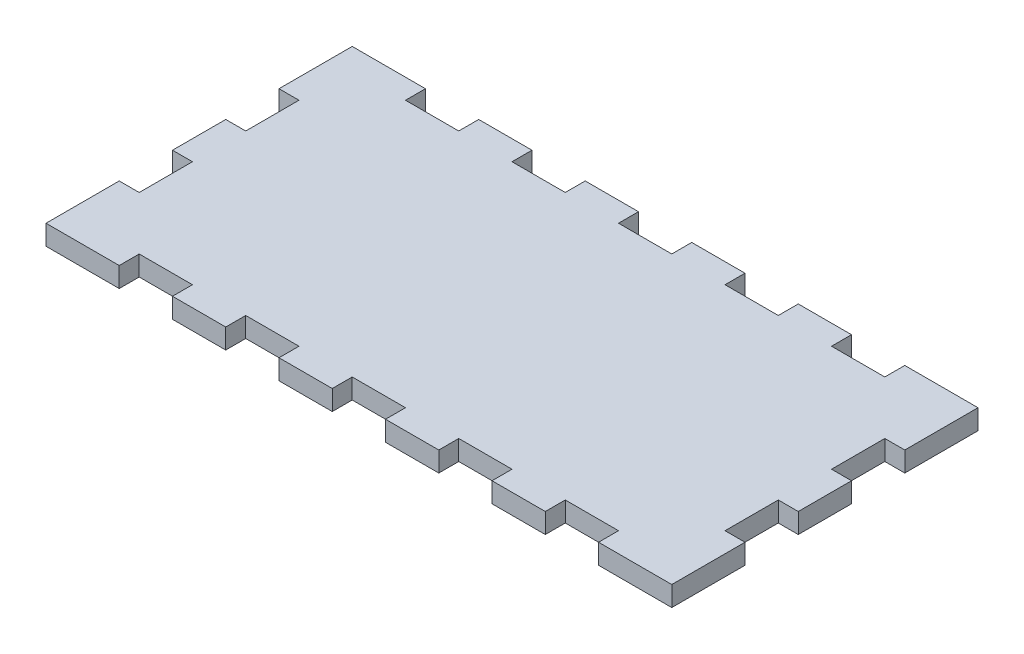
SolidWorks part; units mm, degrees
ref_plane "Front Plane" through (0, 0, 0) normal (0, 0, 1) x (1, 0, 0)
ref_plane "Top Plane" through (0, 0, 0) normal (0, 1, 0) x (1, 0, 0)
ref_plane "Right Plane" through (0, 0, 0) normal (1, 0, 0) x (0, 0, -1)
sketch "Sketch2" plane through (0, 0, 0) normal (0, 1, 0) x (1, 0, 0)
  line L1 (139.7, -63.5) -> (-139.7, -63.5)
  line L2 (139.7, -63.5) -> (139.7, 63.5)
  line L3 (139.7, 63.5) -> (-139.7, 63.5)
  line L4 (-139.7, -63.5) -> (-139.7, 63.5)
  line L5 (139.7, -63.5) -> (-139.7, 63.5) construction
  line L6 (139.7, 63.5) -> (-139.7, -63.5) construction
  point P0 (0, 0)
  dimension "D1" = 279.4
  dimension "D2" = 127
extrude "Boss-Extrude1" add sketch "Sketch2" along normal blind 9.525
sketch "Sketch3" plane through (0, 0, 63.5) normal (0, 0, 1) x (1, 0, 0)
  line L0 (-139.7, 9.525) -> (139.7, 9.525) construction
  line L1 (-139.7, 0) -> (-114.3, 0)
  line L2 (-139.7, 0) -> (-139.7, 9.525)
  line L3 (-139.7, 9.525) -> (-114.3, 9.525)
  line L4 (-114.3, 0) -> (-114.3, 9.525)
  dimension "D1" = 25.4
extrude "Boss-Extrude2" add sketch "Sketch3" along normal blind 9.525
pattern_linear "LPattern1" count 6 spacing 50.8 along (1, 0, 0) of "Boss-Extrude2"
mirror "Mirror1" about plane through (0, 0, 0) normal (0, 0, 1) of "LPattern1"
sketch "Sketch4" plane through (139.7, 0, 0) normal (1, 0, 0) x (0, 0, -1)
  line L0 (-73.025, 0) -> (73.025, 0) construction
  line L1 (-63.5, 0) -> (-38.1, 0)
  line L2 (-63.5, 0) -> (-63.5, 9.525)
  line L3 (-63.5, 9.525) -> (-38.1, 9.525)
  line L4 (-38.1, 0) -> (-38.1, 9.525)
  line L5 (-73.025, 9.525) -> (73.025, 9.525) construction
  line L6 (-73.025, 0) -> (-73.025, 9.525) construction
  dimension "D1" = 9.525
  dimension "D2" = 25.4
extrude "Boss-Extrude3" add sketch "Sketch4" along normal blind 9.525
pattern_linear "LPattern2" count 3 spacing 50.8 along (0, 0, -1) of "Boss-Extrude3"
mirror "Mirror2" about plane through (0, 0, 0) normal (1, 0, 0) of "LPattern2"
sketch "Sketch6" plane through (0, 0, 63.5) normal (0, 0, 1) x (1, 0, 0)
  line L1 (149.225, 9.525) -> (139.7, 9.525)
  line L2 (149.225, 9.525) -> (149.225, 0)
  line L3 (149.225, 0) -> (139.7, 0)
  line L4 (139.7, 9.525) -> (139.7, 0)
extrude "Boss-Extrude4" add sketch "Sketch6" along normal blind 9.525
mirror "Mirror3" about plane through (0, 0, 0) normal (1, 0, 0) of "Boss-Extrude4"
mirror "Mirror4" about plane through (0, 0, 0) normal (0, 0, 1) of "Mirror3"
sketch "Sketch7" plane through (0, 9.525, 0) normal (0, 1, 0) x (1, 0, 0)
  circle A0 centre (-29.2864, 23.8119) radius 0.032
  circle A1 centre (-23.072, 14.7922) radius 0.1056
  circle A2 centre (27.5, 22.9863) radius 2
  circle A3 centre (22.5, 12.9863) radius 2
extrude "Cut-Extrude1" [suppressed] cut sketch "Sketch7" against normal through all
sketch "Sketch8" plane through (0, 9.525, 0) normal (0, 1, 0) x (1, 0, 0)
  circle A0 centre (-25.974, 23.4033) radius 0.0509
  circle A1 centre (-24.0521, 14.3728) radius 0.0812
  circle A2 centre (-27.5, -19.2467) radius 2
  circle A3 centre (-22.5, -29.2467) radius 2
extrude "Cut-Extrude3" [suppressed] cut sketch "Sketch8" against normal through all contours A2 A0 | A3
sketch "Sketch9" [suppressed] plane through (0, 0, 0) normal (0, -1, 0) x (1, 0, 0)
  circle A0 centre (-22.5, -12.9863) radius 3.81
  circle A1 centre (-27.5, -22.9863) radius 3.81
  circle A2 centre (22.5, -12.9863) radius 3.81
  circle A3 centre (27.5, -22.9863) radius 3.81
  dimension "D1" = 7.62
  dimension "D2" = 7.62
  dimension "D3" = 7.62
  dimension "D4" = 7.62
extrude "Cut-Extrude4" [suppressed] cut sketch "Sketch9" against normal blind 4.7625
